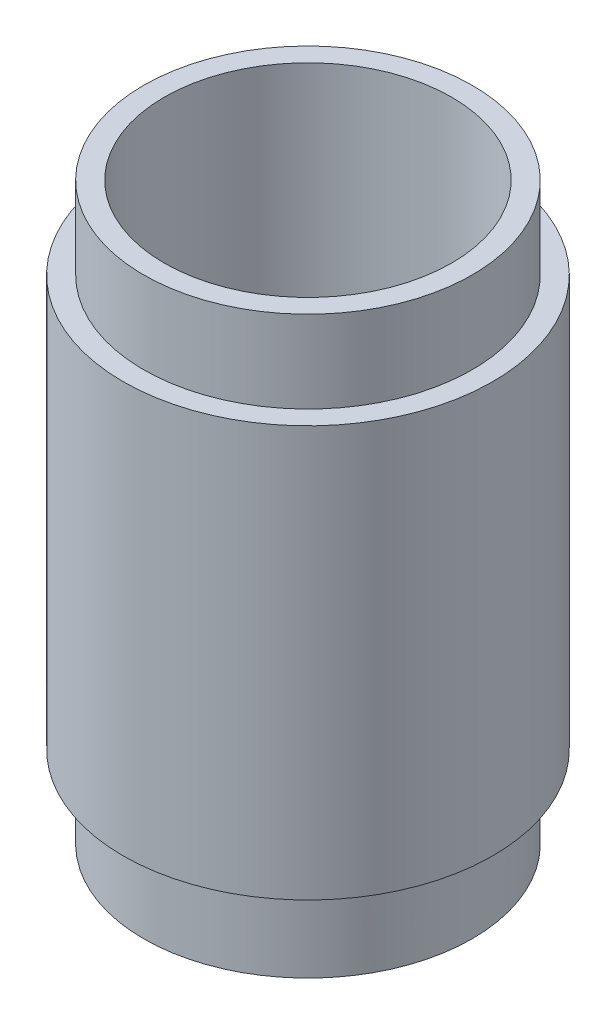
SolidWorks part; units mm, degrees
ref_plane "Front Plane" through (0, 0, 0) normal (0, 0, 1) x (1, 0, 0)
ref_plane "Top Plane" through (0, 0, 0) normal (0, 1, 0) x (1, 0, 0)
ref_plane "Right Plane" through (0, 0, 0) normal (1, 0, 0) x (0, 0, -1)
sketch3d "3DSketch4"
  circle A0 centre (0, 601, 0) radius 45
  circle A1 centre (0, 601, 0) radius 35
  point P2 (0, 646, 0)
  point P5 (0, 636, 0)
extrude "Boss-Extrude3" add sketch "3DSketch4" along direction (0, 1, 0) on the side of the normal blind 100 separate body
sketch "Sketch3" plane through (0, 701, 0) normal (0, 1, 0) x (1, 0, 0)
  circle A0 centre (0, 0) radius 35
  circle A1 centre (0, 0) radius 40
  dimension "D1" = 5
extrude "Boss-Extrude4" add sketch "Sketch3" along normal blind 20
sketch "Sketch4" plane through (0, 601, 0) normal (0, -1, 0) x (1, 0, 0)
  circle A0 centre (0, 0) radius 35
  circle A1 centre (0, 0) radius 40
  dimension "D1" = 5
extrude "Boss-Extrude5" add sketch "Sketch4" along normal blind 20
